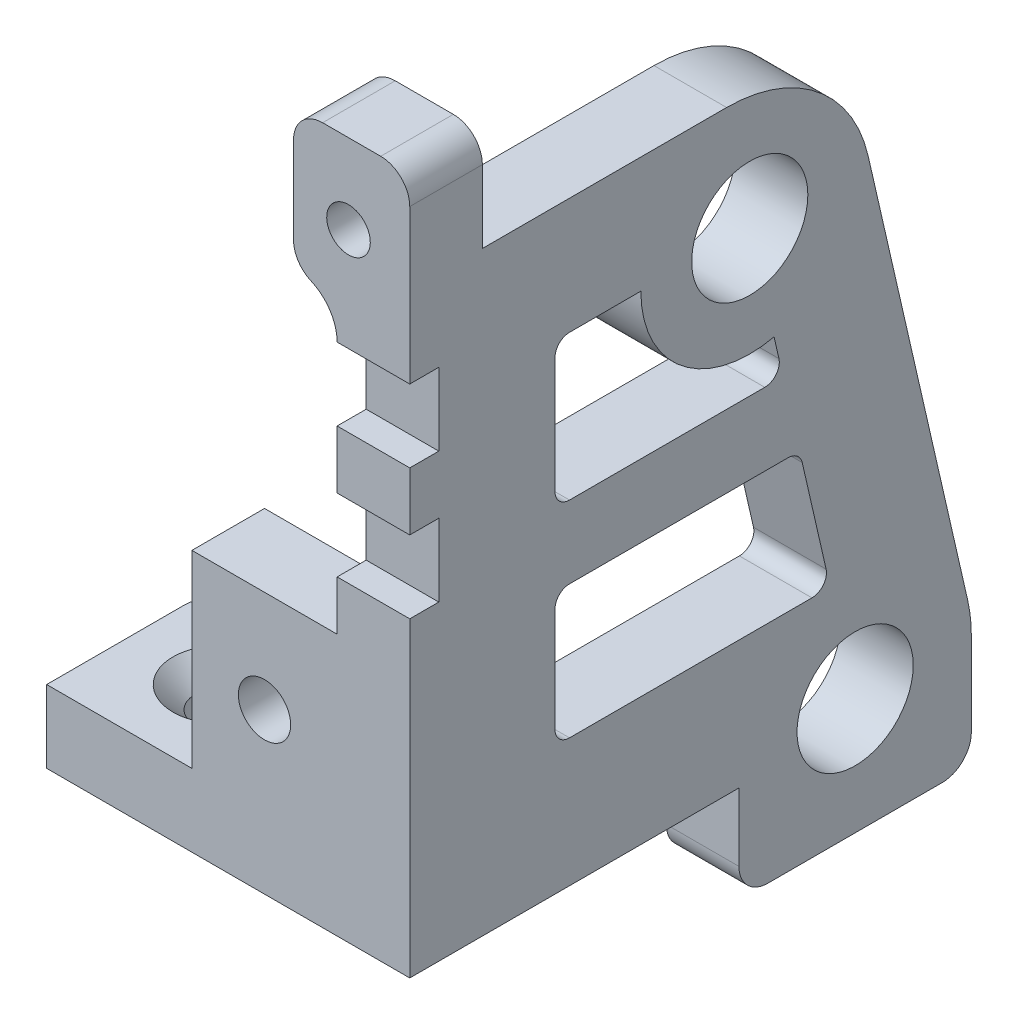
SolidWorks part; units mm, degrees
ref_plane "前视基准面" through (0, 0, 0) normal (0, 0, 1) x (1, 0, 0)
ref_plane "上视基准面" through (0, 0, 0) normal (0, 1, 0) x (1, 0, 0)
ref_plane "右视基准面" through (0, 0, 0) normal (1, 0, 0) x (0, 0, -1)
sketch "草图1" plane through (0, 0, 0) normal (1, 0, 0) x (0, 0, -1)
  line L1 (-23.41, -33) -> (-0.7429, -33)
  line L2 (-0.7429, -33) -> (-0.7429, -39.6794)
  line L3 (-23.41, 8) -> (-23.41, -33)
  line L4 (-23.41, 8) -> (6.3746, 8)
  line L5 (6.3746, 8) -> (15.2571, -30.7748)
  line L6 (15.2571, -30.7748) -> (15.2571, -39.6794)
  line L7 (0, 0) -> (7.2571, -31.6794) construction
  line L8 (-0.7429, -39.6794) -> (15.2571, -39.6794)
  circle A0 centre (0, 0) radius 4
  circle A1 centre (7.2571, -31.6794) radius 4
  dimension "D1" = 23.41
  dimension "D5" = 8
  dimension "D7" = 8
  dimension "D2" = 33
  dimension "D3" = 31.6794
  dimension "D4" = 32.5
  dimension "D6" = 8
  dimension "D8" = 8
  dimension "D9" = 8
  dimension "D10" = 8
extrude "凸台-拉伸1" add sketch "草图1" along normal blind 5
sketch "草图2" plane through (0, 0, 0) normal (-1, 0, 0) x (0, 0, 1)
  line L0 (23.41, -15) -> (23.41, -33)
  line L1 (23.41, 8) -> (23.41, -33) construction
  line L3 (23.41, -33) -> (11.91, -33)
  line L4 (23.41, -33) -> (0.7429, -33) construction
  line L5 (11.91, -33) -> (11.91, -28)
  line L6 (11.91, -28) -> (18.41, -28)
  line L7 (18.41, -28) -> (18.41, -15)
  line L8 (18.41, -15) -> (23.41, -15)
  dimension "D1" = 5
  dimension "D2" = 5
  dimension "D3" = 13
  dimension "D4" = 6.5
extrude "凸台-拉伸2" add sketch "草图2" along normal blind 10
fillet "圆角1" radius 10 2 edges at (2.5, -30.7748, -15.2571) (2.5, 8, -6.3746)
sketch "草图7" plane through (0, 8, 0) normal (0, 1, 0) x (1, 0, 0)
  line L1 (5, -23.41) -> (-3, -23.41)
  line L2 (5, -23.41) -> (5, -18.41)
  line L3 (5, -18.41) -> (-3, -18.41)
  line L4 (-3, -23.41) -> (-3, -18.41)
  dimension "D1" = 5
  dimension "D2" = 8
extrude "凸台-拉伸3" add sketch "草图7" along normal blind 7 and the other way blind 3
hole_wizard "打孔尺寸(%根据十字)槽半沉头木螺钉的类型1" positions "草图3" profile "草图4" countersink size "M3" standard "GB" end condition through all
sketch "草图3" plane through (0, 0, 18.41) normal (0, 0, -1) x (-1, 0, 0)
  line L0 (10, -15) -> (10, -28) construction
  line L1 (10, -28) -> (0, -28) construction
  point P0 (5, -22)
  dimension "D1" = 5
  dimension "D2" = 6
sketch "草图4" plane through (-5, -22, 18.41) normal (1, 0, 0) x (0, 1, 0)
  line L0 (0, 0) -> (0, 5)
  line L1 (0, 5) -> (1.8, 5)
  line L2 (1.8, 5) -> (1.8, 1.5)
  line L3 (1.8, 1.5) -> (3.3, 0)
  line L5 (3.3, 0) -> (0, 0)
  line L6 (-1.8, 1.5) -> (-3.3, 0) construction
  line L11 (0, -6.35) -> (0, 107.95) construction
  dimension "通孔孔直径" = 3.6
  dimension "通孔孔深度" = 5
  dimension "近端锥形沉头孔直径" = 6.6
  dimension "近端锥形沉头孔角度" = 90
fillet "圆角2" radius 2 5 edges at (-3, 5, 20.91) (-3, 15, 20.91) (5, 15, 20.91) (2.5, -39.6794, 0.7429) (2.5, -39.6794, -15.2571)
fillet "圆角3" radius 3 1 edges at (0, 5, 20.91)
hole_wizard "大小mm Transitional 暗销孔1" positions "草图8" profile "草图9" hole size "Ø3.0" standard "GB" end condition through all
sketch "草图8" plane through (0, 0, 18.41) normal (0, 0, -1) x (-1, 0, 0)
  line L0 (-16.2809, 0) -> (3.92, 0) construction
  point P0 (-0.7825, 9.5089)
  dimension "D1" = 0.7825
  dimension "D2" = 9.5089
sketch "草图9" plane through (0.7825, 9.5089, 18.41) normal (1, 0, 0) x (0, 1, 0)
  line L0 (0, 0) -> (0, 5)
  line L1 (0, 5) -> (1.5, 5)
  line L2 (1.5, 5) -> (1.5, 0)
  line L5 (1.5, 0) -> (0, 0)
  line L11 (0, -6.35) -> (0, 107.95) construction
  dimension "通孔孔直径" = 3
  dimension "通孔孔深度" = 5
sketch "草图10" plane through (0, 0, 0) normal (-1, 0, 0) x (0, 0, 1)
  line L1 (23.41, 2.4174) -> (21.41, 2.4174)
  line L2 (23.41, 2.4174) -> (23.41, -2.5826)
  line L3 (23.41, -2.5826) -> (21.41, -2.5826)
  line L4 (21.41, 2.4174) -> (21.41, -2.5826)
  line L5 (23.41, -6.5826) -> (21.41, -6.5826)
  line L6 (23.41, -6.5826) -> (23.41, -11.5826)
  line L7 (23.41, -11.5826) -> (21.41, -11.5826)
  line L8 (21.41, -6.5826) -> (21.41, -11.5826)
  line L9 (23.41, 2.4174) -> (23.41, -15) construction
  dimension "D1" = 2
  dimension "D2" = 5
  dimension "D3" = 5
  dimension "D4" = 4
extrude "切除-拉伸1" cut sketch "草图10" against normal through all
sketch "草图11" plane through (-10, 0, 0) normal (-1, 0, 0) x (0, 0, 1)
  line L1 (11.91, -28) -> (23.41, -28)
  line L2 (11.91, -28) -> (11.91, -33)
  line L3 (11.91, -33) -> (23.41, -33)
  line L4 (23.41, -28) -> (23.41, -33)
extrude "凸台-拉伸4" add sketch "草图11" along normal blind 10
hole_wizard "打孔尺寸(%根据十字)槽半沉头木螺钉的类型2" positions "草图5" profile "草图6" countersink size "M3" standard "GB" end condition through all
sketch "草图5" plane through (0, -28, 0) normal (0, 1, 0) x (1, 0, 0)
  line L0 (-20, -11.91) -> (0, -11.91) construction
  line L3 (-10, -23.41) -> (-10, -18.41) construction
  point P0 (-14, -17.41)
  dimension "D1" = 5.5
  dimension "D2" = 4
sketch "草图6" plane through (-14, -28, 17.41) normal (1, 0, 0) x (0, 0, 1)
  line L0 (0, 0) -> (0, 11.6794)
  line L1 (0, 11.6794) -> (1.8, 11.6794)
  line L2 (1.8, 11.6794) -> (1.8, 1.5)
  line L3 (1.8, 1.5) -> (3.3, 0)
  line L5 (3.3, 0) -> (0, 0)
  line L6 (-1.8, 1.5) -> (-3.3, 0) construction
  line L11 (0, -6.35) -> (0, 107.95) construction
  dimension "通孔孔直径" = 3.6
  dimension "通孔孔深度" = 11.6794
  dimension "近端锥形沉头孔直径" = 6.6
  dimension "近端锥形沉头孔角度" = 90
sketch "草图12" plane through (0, 0, 0) normal (-1, 0, 0) x (0, 0, 1)
  line L0 (7.5, 0) -> (13.41, 0)
  line L1 (13.41, 0) -> (13.41, -10)
  line L2 (-5.539, -24.1794) -> (13.41, -24.1794)
  line L3 (-1.6747, -7.3106) -> (-2.2908, -10)
  line L4 (23.41, -11.5826) -> (23.41, -15) construction
  line L5 (-15.0046, -29.6726) -> (-8.1539, 0.2329) construction
  line L6 (-2.2908, -10) -> (13.41, -10)
  line L7 (-3.4362, -15) -> (13.41, -15)
  line L8 (13.41, -15) -> (13.41, -24.1794)
  line L9 (-3.4362, -15) -> (-5.539, -24.1794)
  arc A0 (-1.6747, -7.3106) -> (7.5, 0) centre (0, 0) ccw
  circle A1 centre (-7.2571, -31.6794) radius 7.5 construction
  point P16 (0, 0)
  point P17 (0, 0)
  dimension "D1" = 15
  dimension "D2" = 10
  dimension "D3" = 5
  dimension "D4" = 10
  dimension "D5" = 8
extrude "切除-拉伸2" cut sketch "草图12" against normal through all
fillet "圆角5" radius 1 7 edges at (2.5, -15, 13.41) (2.5, -24.1794, 13.41) (2.5, -24.1794, -5.539) (2.5, -15, -3.4362) (2.5, -10, -2.2908) (2.5, -10, 13.41) (2.5, 0, 13.41)
fillet "圆角6" radius 2 1 edges at (-20, -30.5, 11.91)
sketch "草图13" plane through (0, -33, 0) normal (0, -1, 0) x (1, 0, 0)
  line L0 (-18, 11.91) -> (0, 11.91) construction
  line L1 (-16.5, 11.91) -> (-20, 11.91)
  line L2 (-16.5, 11.91) -> (-16.5, 16.91)
  line L3 (-16.5, 16.91) -> (-20, 16.91)
  line L4 (-20, 11.91) -> (-20, 16.91)
  line L5 (-20, 13.91) -> (-20, 23.41) construction
  dimension "D1" = 3.5
  dimension "D2" = 5
extrude "切除-拉伸3" cut sketch "草图13" against normal blind 0.5
